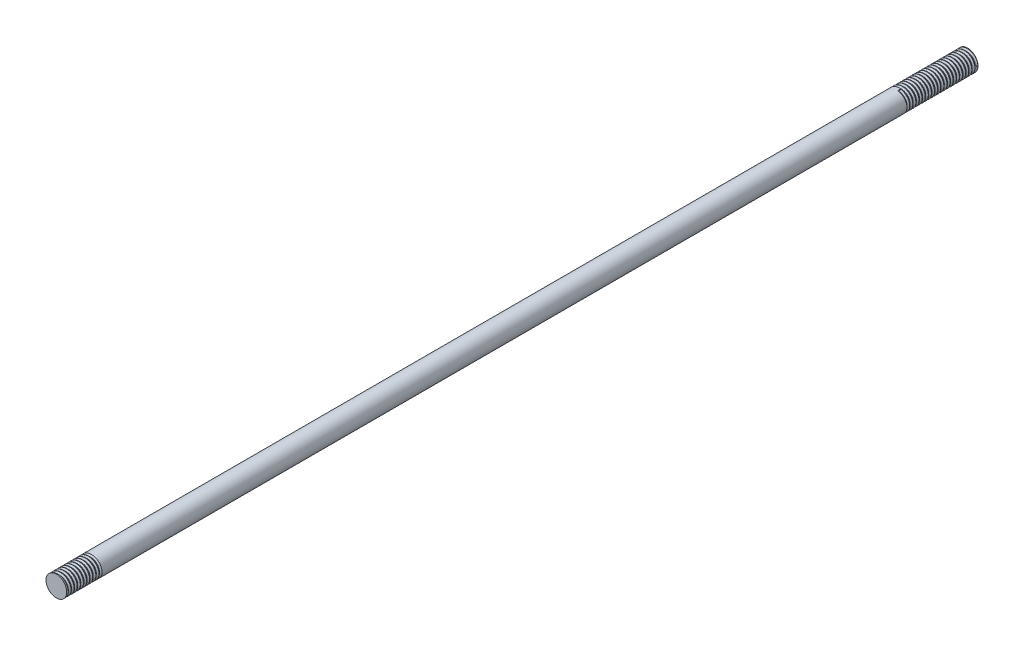
SolidWorks part; units mm, degrees
ref_plane "Alzado" through (0, 0, 0) normal (0, 0, 1) x (1, 0, 0)
ref_plane "Planta" through (0, 0, 0) normal (0, 1, 0) x (1, 0, 0)
ref_plane "Vista lateral" through (0, 0, 0) normal (1, 0, 0) x (0, 0, -1)
sketch "Croquis1" plane through (0, 0, 0) normal (0, 0, 1) x (1, 0, 0)
  circle A0 centre (0, 0) radius 1.5
  dimension "D1" = 3
extrude "Saliente-Extruir1" add sketch "Croquis1" along normal blind 132
cosmetic thread "Rosca cosmética1"
thread "Rosca1" pitch 0.45 method cut profile "Perfil de rosca1" start angle 0, offset 0, length 5, pitch 0.45, diameter 3
ref_plane "Plano1" through (-1.5, 0, 132) normal (0, -1, 0) x (-1, 0, 0)
sketch "Perfil de rosca1" plane through (-1.5, 0, 132) normal (0, -1, 0) x (-1, 0, 0)
  line L0 (0, 0) -> (0, 0.45) construction
  line L11 (0, 0) -> (0, 0.3937)
  line L12 (0, 0.3937) -> (-0.2436, 0.2531)
  line L13 (-0.2436, 0.2531) -> (-0.2436, 0.1406)
  line L15 (-0.2436, 0.1406) -> (0, 0)
  line L17 (-0.2436, 0.1969) -> (0, 0.1969) construction
  point P2 (0, 0)
  dimension "Pitch" = 0.45
  dimension "Profile_Angle" = 60
  dimension "Profile_Land" = 0.1125
  dimension "Profile_Height" = 0.2436
thread "Rosca2" pitch 0.45 method cut profile "Perfil de rosca2" start angle 0, offset 0, length 10, pitch 0.45, diameter 3
ref_plane "Plano2" through (1.5, 0, 0) normal (0, -1, 0) x (1, 0, 0)
sketch "Perfil de rosca2" plane through (1.5, 0, 0) normal (0, -1, 0) x (1, 0, 0)
  line L0 (0, 0) -> (0, 0.45) construction
  line L11 (0, 0) -> (0, 0.3937)
  line L12 (0, 0.3937) -> (-0.2436, 0.2531)
  line L13 (-0.2436, 0.2531) -> (-0.2436, 0.1406)
  line L15 (-0.2436, 0.1406) -> (0, 0)
  line L17 (-0.2436, 0.1969) -> (0, 0.1969) construction
  point P2 (0, 0)
  dimension "Pitch" = 0.45
  dimension "Profile_Angle" = 60
  dimension "Profile_Land" = 0.1125
  dimension "Profile_Height" = 0.2436
equation "\"D1@Saliente-Extruir1\"=132"
